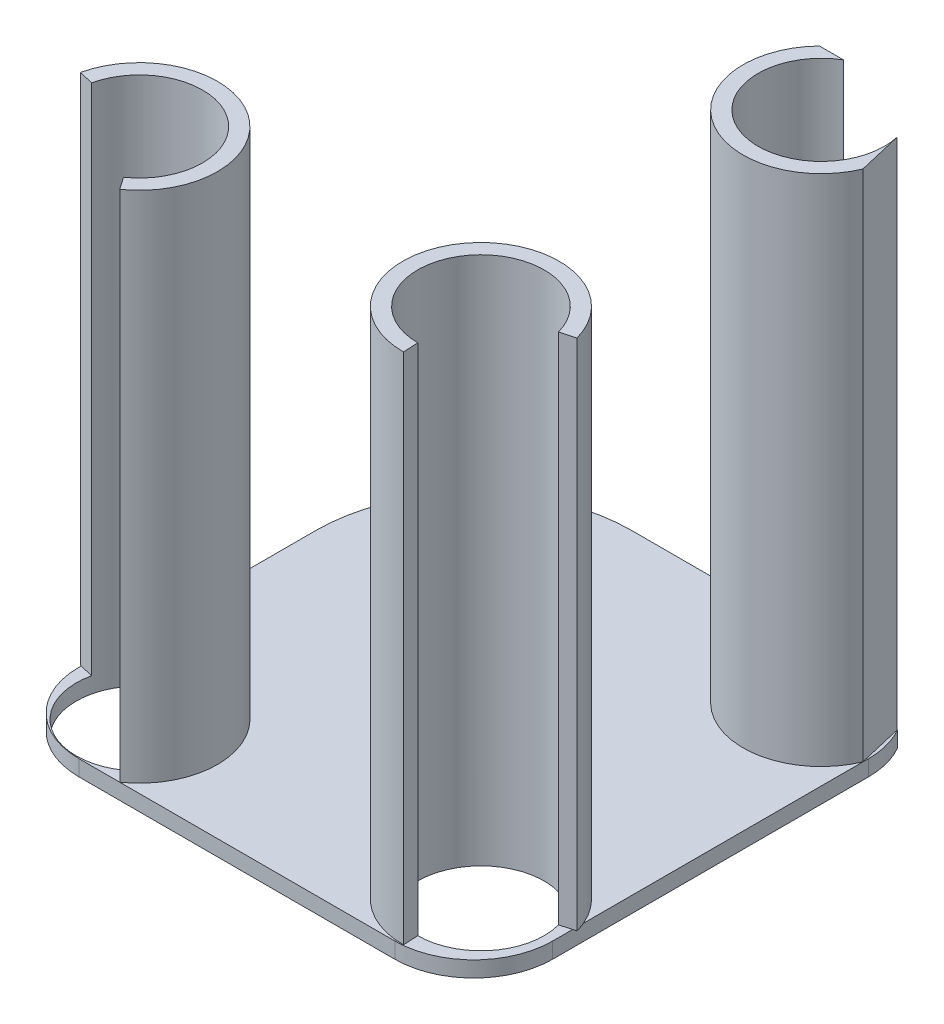
SolidWorks part; units mm, degrees
ref_plane "Front Plane" through (0, 0, 0) normal (0, 0, 1) x (1, 0, 0)
ref_plane "Top Plane" through (0, 0, 0) normal (0, 1, 0) x (1, 0, 0)
ref_plane "Right Plane" through (0, 0, 0) normal (1, 0, 0) x (0, 0, -1)
sketch "Sketch2" plane through (0, 0, 0) normal (0, 1, 0) x (1, 0, 0)
  line L1 (-10, 30) -> (20, 30)
  line L2 (-30, 10) -> (-30, -20)
  line L3 (-20, -30) -> (20, -30)
  line L4 (30, 20) -> (30, -20)
  line L5 (-30, 30) -> (30, -30) construction
  line L6 (-30, -30) -> (30, 30) construction
  arc A0 (-10, 30) -> (-30, 10) centre (-10, 10) ccw
  arc A1 (-30, -20) -> (-20, -30) centre (-20, -20) ccw
  arc A2 (20, -30) -> (30, -20) centre (20, -20) ccw
  arc A3 (20, 30) -> (30, 20) centre (20, 20) cw
  point P0 (0, 0)
  dimension "D3" = 20
  dimension "D4" = 10
  dimension "D1" = 60
  dimension "D2" = 60
extrude "Boss-Extrude1" add sketch "Sketch2" along normal blind 2
sketch "Sketch4" plane through (0, 2, 0) normal (0, 1, 0) x (1, 0, 0)
  circle A0 centre (-22.4496, -20.0472) radius 11
  circle A1 centre (20.5475, -19.2406) radius 11
  circle A2 centre (19.8692, 19.7716) radius 11
  point P9 (-22.4496, -20.0472)
  point P10 (0, 0)
  point P11 (0, 0)
  dimension "D1" = 22
extrude "Boss-Extrude8" [suppressed] add sketch "Sketch4" along normal blind 65
sketch "Sketch3" plane through (0, 2, 0) normal (0, 1, 0) x (1, 0, 0)
  circle A0 centre (-22.4496, -20.0472) radius 7.5566
  circle A2 centre (20.5475, -19.2406) radius 7.5566
  circle A4 centre (19.8692, 19.7716) radius 7.5566
extrude "Cut-Extrude2" [suppressed] cut sketch "Sketch3" against normal through all and the other way through all
sketch "Sketch5" plane through (0, 2, 0) normal (0, 1, 0) x (1, 0, 0)
  line L0 (-30.1164, -19.6808) -> (-28.2634, -20.1009)
  line L1 (-14.8127, -30) -> (-15.8968, -28.4396)
  line L2 (-20, -30) -> (20, -30) construction
  line L3 (20.9771, -29.8639) -> (20.8756, -27.9644)
  line L4 (28.5957, -17.8666) -> (30.4292, -17.3683)
  line L5 (13.7644, 30) -> (16.8063, 30)
  line L7 (20, 30) -> (-10, 30) construction
  line L8 (28.6649, 24.9363) -> (29.9945, 19.2581)
  arc A0 (-15.8968, -28.4396) -> (-28.2634, -20.1009) centre (-20.4614, -21.8697) ccw
  arc A1 (28.5957, -17.8666) -> (20.8756, -27.9644) centre (20.8756, -19.9644) ccw
  arc A2 (16.8063, 30) -> (28.6649, 24.9363) centre (20.8756, 23.1123) ccw
  arc A3 (13.7644, 30) -> (29.9945, 19.2581) centre (20.8756, 23.1123) ccw
  arc A4 (30.4292, -17.3683) -> (20.9771, -29.8639) centre (20.8756, -19.9644) ccw
  arc A5 (-14.8127, -30) -> (-30.1164, -19.6808) centre (-20.4614, -21.8697) ccw
  dimension "D1" = 16
  dimension "D2" = 1.9
extrude "Boss-Extrude9" add sketch "Sketch5" along normal blind 65
sketch "Sketch6" plane through (0, 2, 0) normal (0, 1, 0) x (1, 0, 0)
  circle A0 centre (20.8756, 23.1123) radius 8
  circle A1 centre (-20.4614, -21.8697) radius 8
  circle A2 centre (20.8756, -19.9644) radius 8
  circle A3 centre (-20.4614, -21.8697) radius 8 construction
extrude "Cut-Extrude3" cut sketch "Sketch6" against normal through all
sketch "Sketch7" plane through (0, 0, 0) normal (0, -1, 0) x (1, 0, 0)
  circle A0 centre (6.6002, -6.0679) radius 2
  dimension "D1" = 4
extrude "Boss-Extrude10" add sketch "Sketch7" along normal blind 10
sketch "Sketch8" plane through (0, 0, 0) normal (0, -1, 0) x (1, 0, 0)
  circle A0 centre (-5.4015, 9.1209) radius 2
  dimension "D1" = 4
extrude "Boss-Extrude11" add sketch "Sketch8" along normal blind 10
